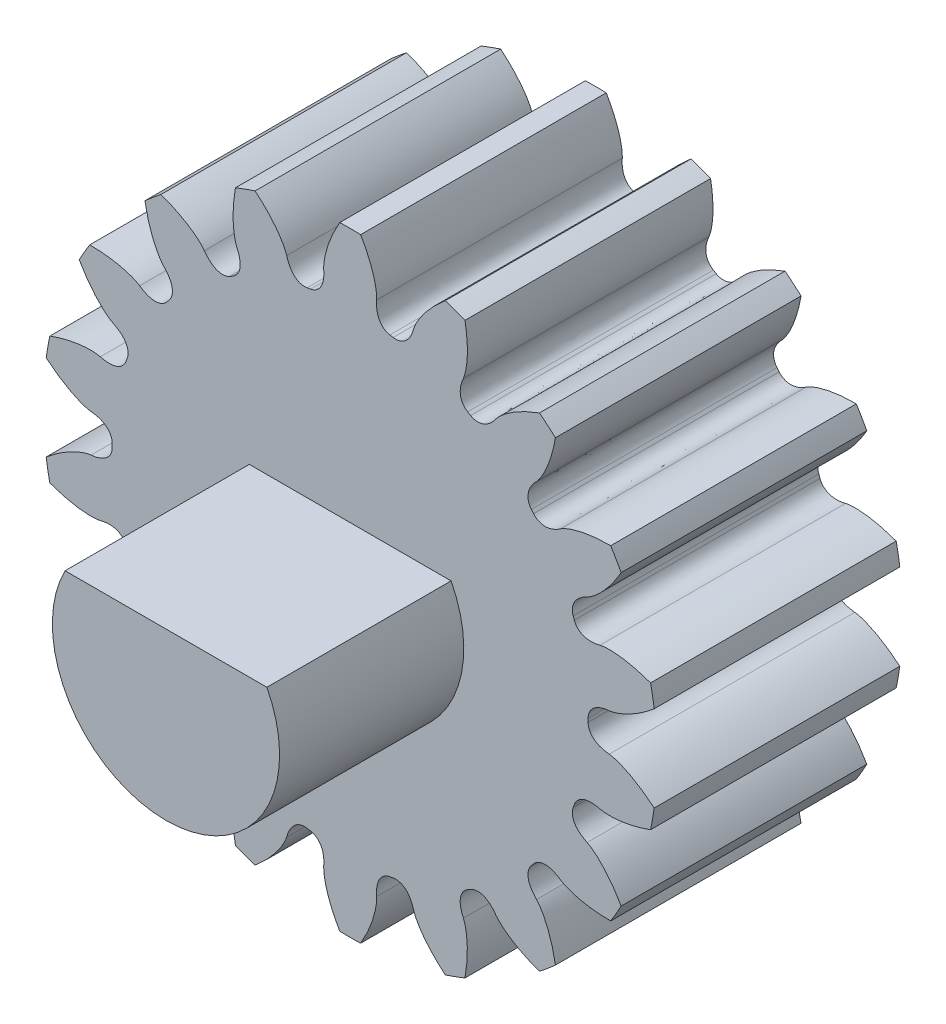
SolidWorks part; units mm, degrees
ref_plane "Спереди" through (0, 0, 0) normal (0, 0, 1) x (1, 0, 0)
ref_plane "Сверху" through (0, 0, 0) normal (0, 1, 0) x (1, 0, 0)
ref_plane "Справа" through (0, 0, 0) normal (1, 0, 0) x (0, 0, -1)
sketch "Sketch1" plane through (0, 0, 0) normal (0, 0, 1) x (1, 0, 0)
  circle A0 centre (0, 0) radius 5.5
extrude "Extrude1" add sketch "Sketch1" along normal blind 4
sketch "Sketch2" plane through (0, 0, 4) normal (0, 0, 1) x (1, 0, 0)
  line L0 (1.6432, 0.85) -> (-1.6432, 0.85)
  line L1 (1.7321, 1) -> (-1.7321, 1)
  arc A0 (-1.7321, 1) -> (1.7321, 1) centre (0, 0) ccw
  arc A1 (-1.6432, 0.85) -> (1.6432, 0.85) centre (0, 0) ccw
  dimension "D1" = 0.15
extrude "Extrude2" add sketch "Sketch2" along normal blind 3 contours L0 A1 region at (0, -0.3518, 4)
sketch "Sketch3" plane through (0, 0, 0) normal (0, 0, -1) x (-1, 0, 0)
  line L0 (1.1832, 1.15) -> (-1.1832, 1.15)
  line L1 (1.118, 1) -> (-1.118, 1)
  arc A0 (-1.118, 1) -> (1.118, 1) centre (0, 0) ccw
  arc A1 (-1.1832, 1.15) -> (1.1832, 1.15) centre (0, 0) ccw
  dimension "D1" = 0.15
extrude "Extrude3" cut sketch "Sketch3" against normal blind 3.5 contours L1 A0 | A0 L1 | L0 A1 A0 L1 region at (0, -1.6067, 0) region at (0, -0.148, 0)
sketch "Sketch4" plane through (0, 0, 0) normal (0, 0, 1) x (1, 0, 0)
  line L0 (0, 0) -> (0, 6.5) construction
  line L1 (0, 0) -> (0, -6.5) construction
  line L2 (0, 0) -> (-6.5, 0) construction
  line L3 (0, 0) -> (6.5, 0) construction
  arc A28 (-0.6456, 3.8208) -> (-0.7002, 3.8112) centre (0, 0) ccw
  arc A30 (-1.549, 4.754) -> (-1.8692, 4.6375) centre (0, 0) ccw
  arc A31 (-1.9135, 3.3696) -> (-1.9614, 3.3419) centre (0, 0) ccw
  arc A32 (-3.0816, 3.9375) -> (-3.3426, 3.7185) centre (0, 0) ccw
  arc A33 (-2.9505, 2.512) -> (-2.9862, 2.4695) centre (0, 0) ccw
  arc A34 (-4.2424, 2.6461) -> (-4.4128, 2.351) centre (0, 0) ccw
  arc A35 (-3.6317, 1.3513) -> (-3.6507, 1.2993) centre (0, 0) ccw
  arc A36 (-4.8916, 1.0355) -> (-4.9508, 0.6999) centre (0, 0) ccw
  arc A37 (-3.8749, 0.0277) -> (-3.8749, -0.0277) centre (0, 0) ccw
  arc A38 (-4.9508, -0.6999) -> (-4.8916, -1.0355) centre (0, 0) ccw
  arc A39 (-3.6507, -1.2993) -> (-3.6317, -1.3513) centre (0, 0) ccw
  arc A40 (-4.4128, -2.351) -> (-4.2424, -2.6461) centre (0, 0) ccw
  arc A41 (-2.9862, -2.4695) -> (-2.9505, -2.512) centre (0, 0) ccw
  arc A42 (-3.3426, -3.7185) -> (-3.0816, -3.9375) centre (0, 0) ccw
  arc A43 (-1.9614, -3.3419) -> (-1.9135, -3.3696) centre (0, 0) ccw
  arc A44 (-1.8692, -4.6375) -> (-1.549, -4.754) centre (0, 0) ccw
  arc A45 (-0.7002, -3.8112) -> (-0.6456, -3.8208) centre (0, 0) ccw
  arc A46 (-0.1704, -4.9971) -> (0.1704, -4.9971) centre (0, 0) ccw
  arc A47 (0.6456, -3.8208) -> (0.7002, -3.8112) centre (0, 0) ccw
  arc A48 (1.549, -4.754) -> (1.8692, -4.6375) centre (0, 0) ccw
  arc A49 (1.9135, -3.3696) -> (1.9614, -3.3419) centre (0, 0) ccw
  arc A50 (3.0816, -3.9375) -> (3.3426, -3.7185) centre (0, 0) ccw
  arc A51 (2.9505, -2.512) -> (2.9862, -2.4695) centre (0, 0) ccw
  arc A52 (4.2424, -2.6461) -> (4.4128, -2.351) centre (0, 0) ccw
  arc A53 (3.6317, -1.3513) -> (3.6507, -1.2993) centre (0, 0) ccw
  arc A54 (4.8916, -1.0355) -> (4.9508, -0.6999) centre (0, 0) ccw
  arc A55 (3.8749, -0.0277) -> (3.8749, 0.0277) centre (0, 0) ccw
  arc A56 (4.9508, 0.6999) -> (4.8916, 1.0355) centre (0, 0) ccw
  arc A57 (3.6507, 1.2993) -> (3.6317, 1.3513) centre (0, 0) ccw
  arc A58 (4.4128, 2.351) -> (4.2424, 2.6461) centre (0, 0) ccw
  arc A59 (2.9862, 2.4695) -> (2.9505, 2.512) centre (0, 0) ccw
  arc A60 (3.3426, 3.7185) -> (3.0816, 3.9375) centre (0, 0) ccw
  arc A61 (1.9614, 3.3419) -> (1.9135, 3.3696) centre (0, 0) ccw
  arc A62 (1.8692, 4.6375) -> (1.549, 4.754) centre (0, 0) ccw
  arc A63 (0.7002, 3.8112) -> (0.6456, 3.8208) centre (0, 0) ccw
  circle A64 centre (0, 0) radius 4.5 construction
  arc A65 (0.1704, 4.9971) -> (-0.1704, 4.9971) centre (0, 0) ccw
  circle A66 centre (0, 0) radius 6.3388
  spline S0 degree 3 poles (0.4314, 4.2073) (0.4264, 4.1628) (0.4271, 4.1189) (0.4335, 4.0758) (0.4372, 4.0511) (0.4421, 4.026) (0.4501, 4.0023) (0.4558, 3.9851) (0.4628, 3.968) (0.4713, 3.952) (0.4783, 3.9388) (0.4864, 3.9259) (0.4954, 3.914) (0.5034, 3.9034) (0.5123, 3.8933) (0.5218, 3.8841) (0.5307, 3.8755) (0.5403, 3.8675) (0.5504, 3.8604) (0.56, 3.8536) (0.5702, 3.8474) (0.5807, 3.8421) (0.5909, 3.837) (0.6017, 3.8326) (0.6125, 3.829) (0.6233, 3.8255) (0.6343, 3.8228) (0.6456, 3.8208) knots 0 0 0 0 1 1 1 2 2 2 3 3 3 4 4 4 5 5 5 6 6 6 7 7 7 8 8 8 9 9 9 9
  spline S1 degree 3 poles (-0.4314, 4.2073) (-0.4264, 4.1628) (-0.4271, 4.1189) (-0.4335, 4.0758) (-0.4372, 4.0511) (-0.4421, 4.026) (-0.4501, 4.0023) (-0.4558, 3.9851) (-0.4628, 3.968) (-0.4713, 3.952) (-0.4783, 3.9388) (-0.4864, 3.9259) (-0.4954, 3.914) (-0.5034, 3.9034) (-0.5123, 3.8933) (-0.5218, 3.8841) (-0.5307, 3.8755) (-0.5403, 3.8675) (-0.5504, 3.8604) (-0.56, 3.8536) (-0.5702, 3.8474) (-0.5807, 3.8421) (-0.5909, 3.837) (-0.6017, 3.8326) (-0.6125, 3.829) (-0.6233, 3.8255) (-0.6343, 3.8228) (-0.6456, 3.8208) knots 0 0 0 0 1 1 1 2 2 2 3 3 3 4 4 4 5 5 5 6 6 6 7 7 7 8 8 8 9 9 9 9
  spline S2 degree 3 poles (0.4314, 4.2073) (0.432, 4.2362) (0.431, 4.265) (0.4284, 4.2936) (0.4258, 4.3229) (0.4209, 4.352) (0.4156, 4.3809) (0.4101, 4.4104) (0.4034, 4.4397) (0.3959, 4.4687) (0.3884, 4.4983) (0.3797, 4.5277) (0.3705, 4.5568) (0.361, 4.5865) (0.3507, 4.6159) (0.3398, 4.6451) (0.3287, 4.6748) (0.3167, 4.7042) (0.3042, 4.7333) (0.2915, 4.763) (0.278, 4.7924) (0.264, 4.8215) (0.2497, 4.8511) (0.2348, 4.8805) (0.2193, 4.9095) (0.2036, 4.939) (0.1873, 4.9682) (0.1704, 4.9971) knots 0 0 0 0 1 1 1 2 2 2 3 3 3 4 4 4 5 5 5 6 6 6 7 7 7 8 8 8 9 9 9 9
  spline S3 degree 3 poles (-0.4314, 4.2073) (-0.432, 4.2362) (-0.431, 4.265) (-0.4284, 4.2936) (-0.4258, 4.3229) (-0.4209, 4.352) (-0.4156, 4.3809) (-0.4101, 4.4104) (-0.4034, 4.4397) (-0.3959, 4.4687) (-0.3884, 4.4983) (-0.3797, 4.5277) (-0.3705, 4.5568) (-0.361, 4.5865) (-0.3507, 4.6159) (-0.3398, 4.6451) (-0.3287, 4.6748) (-0.3167, 4.7042) (-0.3042, 4.7333) (-0.2915, 4.763) (-0.278, 4.7924) (-0.264, 4.8215) (-0.2497, 4.8511) (-0.2348, 4.8805) (-0.2193, 4.9095) (-0.2036, 4.939) (-0.1873, 4.9682) (-0.1704, 4.9971) knots 0 0 0 0 1 1 1 2 2 2 3 3 3 4 4 4 5 5 5 6 6 6 7 7 7 8 8 8 9 9 9 9
  spline S4 degree 3 poles (-1.0336, 4.1011) (-1.0231, 4.0576) (-1.0074, 4.0166) (-0.9866, 3.9783) (-0.9747, 3.9563) (-0.9616, 3.9344) (-0.9459, 3.9148) (-0.9346, 3.9007) (-0.9223, 3.887) (-0.9088, 3.8748) (-0.8977, 3.8649) (-0.8857, 3.8555) (-0.8732, 3.8474) (-0.862, 3.8402) (-0.8502, 3.8337) (-0.8381, 3.8283) (-0.8268, 3.8233) (-0.8151, 3.819) (-0.8032, 3.8158) (-0.7918, 3.8127) (-0.7801, 3.8104) (-0.7684, 3.809) (-0.757, 3.8077) (-0.7454, 3.8072) (-0.734, 3.8076) (-0.7227, 3.808) (-0.7114, 3.8092) (-0.7002, 3.8112) knots 0 0 0 0 1 1 1 2 2 2 3 3 3 4 4 4 5 5 5 6 6 6 7 7 7 8 8 8 9 9 9 9
  spline S5 degree 3 poles (-1.8443, 3.806) (-1.8244, 3.7659) (-1.8101, 3.7245) (-1.8014, 3.6817) (-1.7963, 3.6572) (-1.7924, 3.632) (-1.7918, 3.607) (-1.7913, 3.5888) (-1.792, 3.5704) (-1.7945, 3.5525) (-1.7966, 3.5377) (-1.7998, 3.5228) (-1.8042, 3.5085) (-1.8081, 3.4958) (-1.813, 3.4833) (-1.8188, 3.4714) (-1.8242, 3.4603) (-1.8305, 3.4495) (-1.8375, 3.4393) (-1.8442, 3.4297) (-1.8517, 3.4204) (-1.8598, 3.4118) (-1.8676, 3.4035) (-1.8762, 3.3956) (-1.8852, 3.3886) (-1.8941, 3.3816) (-1.9035, 3.3753) (-1.9135, 3.3696) knots 0 0 0 0 1 1 1 2 2 2 3 3 3 4 4 4 5 5 5 6 6 6 7 7 7 8 8 8 9 9 9 9
  spline S6 degree 3 poles (-1.0336, 4.1011) (-1.043, 4.1285) (-1.0537, 4.1552) (-1.066, 4.1812) (-1.0784, 4.2078) (-1.093, 4.2335) (-1.1079, 4.2588) (-1.123, 4.2847) (-1.1394, 4.3099) (-1.1563, 4.3346) (-1.1736, 4.3599) (-1.1917, 4.3845) (-1.2104, 4.4087) (-1.2294, 4.4334) (-1.2492, 4.4575) (-1.2694, 4.4811) (-1.29, 4.5052) (-1.3113, 4.5288) (-1.333, 4.5519) (-1.3551, 4.5755) (-1.3779, 4.5985) (-1.401, 4.621) (-1.4245, 4.644) (-1.4486, 4.6664) (-1.473, 4.6884) (-1.4979, 4.7108) (-1.5232, 4.7326) (-1.549, 4.754) knots 0 0 0 0 1 1 1 2 2 2 3 3 3 4 4 4 5 5 5 6 6 6 7 7 7 8 8 8 9 9 9 9
  spline S7 degree 3 poles (-1.8443, 3.806) (-1.8548, 3.833) (-1.8637, 3.8604) (-1.8711, 3.8882) (-1.8786, 3.9166) (-1.884, 3.9456) (-1.8889, 3.9746) (-1.8938, 4.0041) (-1.8975, 4.034) (-1.9004, 4.0638) (-1.9034, 4.0942) (-1.9054, 4.1248) (-1.9067, 4.1553) (-1.9079, 4.1864) (-1.9083, 4.2176) (-1.908, 4.2487) (-1.9077, 4.2804) (-1.9065, 4.3122) (-1.9048, 4.3438) (-1.903, 4.3761) (-1.9004, 4.4083) (-1.8971, 4.4404) (-1.8939, 4.4732) (-1.8899, 4.5058) (-1.8853, 4.5384) (-1.8806, 4.5715) (-1.8752, 4.6045) (-1.8692, 4.6375) knots 0 0 0 0 1 1 1 2 2 2 3 3 3 4 4 4 5 5 5 6 6 6 7 7 7 8 8 8 9 9 9 9
  spline S8 degree 3 poles (-2.3739, 3.5002) (-2.3491, 3.463) (-2.3204, 3.4298) (-2.2878, 3.4009) (-2.2691, 3.3843) (-2.2492, 3.3682) (-2.2278, 3.3552) (-2.2124, 3.3458) (-2.1961, 3.3371) (-2.1792, 3.3303) (-2.1654, 3.3248) (-2.151, 3.32) (-2.1364, 3.3167) (-2.1234, 3.3138) (-2.1101, 3.3117) (-2.0969, 3.3108) (-2.0846, 3.3099) (-2.0721, 3.31) (-2.0598, 3.311) (-2.0481, 3.312) (-2.0363, 3.3138) (-2.0248, 3.3165) (-2.0137, 3.3191) (-2.0026, 3.3226) (-1.992, 3.3269) (-1.9815, 3.3311) (-1.9713, 3.3361) (-1.9614, 3.3419) knots 0 0 0 0 1 1 1 2 2 2 3 3 3 4 4 4 5 5 5 6 6 6 7 7 7 8 8 8 9 9 9 9
  spline S9 degree 3 poles (-3.0348, 2.9457) (-3.0024, 2.9148) (-2.9748, 2.8807) (-2.952, 2.8436) (-2.9389, 2.8223) (-2.9265, 2.7999) (-2.9174, 2.7766) (-2.9108, 2.7597) (-2.9051, 2.7422) (-2.9013, 2.7245) (-2.8982, 2.7098) (-2.8961, 2.6948) (-2.8954, 2.6799) (-2.8947, 2.6666) (-2.895, 2.6531) (-2.8964, 2.6399) (-2.8977, 2.6277) (-2.8999, 2.6154) (-2.903, 2.6035) (-2.906, 2.5921) (-2.9098, 2.5808) (-2.9145, 2.57) (-2.919, 2.5595) (-2.9244, 2.5492) (-2.9305, 2.5394) (-2.9364, 2.5298) (-2.9431, 2.5207) (-2.9505, 2.512) knots 0 0 0 0 1 1 1 2 2 2 3 3 3 4 4 4 5 5 5 6 6 6 7 7 7 8 8 8 9 9 9 9
  spline S10 degree 3 poles (-2.3739, 3.5002) (-2.3921, 3.5228) (-2.4113, 3.5442) (-2.4317, 3.5645) (-2.4525, 3.5852) (-2.475, 3.6044) (-2.4977, 3.6231) (-2.5208, 3.6422) (-2.5448, 3.6603) (-2.5691, 3.6777) (-2.594, 3.6955) (-2.6195, 3.7125) (-2.6453, 3.7289) (-2.6716, 3.7455) (-2.6984, 3.7614) (-2.7255, 3.7767) (-2.7531, 3.7923) (-2.7812, 3.8072) (-2.8095, 3.8215) (-2.8383, 3.836) (-2.8675, 3.8499) (-2.897, 3.8632) (-2.9269, 3.8767) (-2.9572, 3.8896) (-2.9877, 3.9019) (-3.0187, 3.9144) (-3.05, 3.9263) (-3.0816, 3.9375) knots 0 0 0 0 1 1 1 2 2 2 3 3 3 4 4 4 5 5 5 6 6 6 7 7 7 8 8 8 9 9 9 9
  spline S11 degree 3 poles (-3.0348, 2.9457) (-3.0539, 2.9675) (-3.0716, 2.9902) (-3.0881, 3.0137) (-3.1049, 3.0378) (-3.1199, 3.0633) (-3.1343, 3.0889) (-3.1491, 3.1149) (-3.1627, 3.1417) (-3.1757, 3.1687) (-3.189, 3.1963) (-3.2012, 3.2243) (-3.2129, 3.2526) (-3.2247, 3.2814) (-3.2357, 3.3106) (-3.2461, 3.3399) (-3.2566, 3.3698) (-3.2664, 3.4) (-3.2756, 3.4304) (-3.2849, 3.4613) (-3.2935, 3.4925) (-3.3015, 3.5238) (-3.3096, 3.5557) (-3.317, 3.5877) (-3.3238, 3.6199) (-3.3307, 3.6526) (-3.337, 3.6855) (-3.3426, 3.7185) knots 0 0 0 0 1 1 1 2 2 2 3 3 3 4 4 4 5 5 5 6 6 6 7 7 7 8 8 8 9 9 9 9
  spline S12 degree 3 poles (-3.4279, 2.4772) (-3.3919, 2.4507) (-3.3535, 2.4294) (-3.313, 2.4133) (-3.2897, 2.4041) (-3.2656, 2.3958) (-3.241, 2.3909) (-3.2233, 2.3873) (-3.205, 2.3848) (-3.1869, 2.3842) (-3.1719, 2.3837) (-3.1568, 2.3841) (-3.1419, 2.386) (-3.1288, 2.3877) (-3.1155, 2.3903) (-3.1028, 2.3939) (-3.0909, 2.3974) (-3.0792, 2.4017) (-3.068, 2.4068) (-3.0573, 2.4117) (-3.0469, 2.4175) (-3.037, 2.424) (-3.0275, 2.4303) (-3.0183, 2.4373) (-3.0097, 2.445) (-3.0013, 2.4525) (-2.9935, 2.4607) (-2.9862, 2.4695) knots 0 0 0 0 1 1 1 2 2 2 3 3 3 4 4 4 5 5 5 6 6 6 7 7 7 8 8 8 9 9 9 9
  spline S13 degree 3 poles (-3.8593, 1.7301) (-3.8183, 1.7121) (-3.7807, 1.6896) (-3.7465, 1.6625) (-3.7269, 1.6469) (-3.7076, 1.6301) (-3.6911, 1.6114) (-3.6791, 1.5978) (-3.6678, 1.5832) (-3.6582, 1.5678) (-3.6503, 1.5551) (-3.6431, 1.5418) (-3.6373, 1.528) (-3.6322, 1.5157) (-3.6278, 1.503) (-3.6246, 1.4901) (-3.6216, 1.4782) (-3.6195, 1.4658) (-3.6184, 1.4536) (-3.6173, 1.4419) (-3.617, 1.4299) (-3.6177, 1.4182) (-3.6184, 1.4067) (-3.6199, 1.3952) (-3.6223, 1.384) (-3.6246, 1.373) (-3.6278, 1.3621) (-3.6317, 1.3513) knots 0 0 0 0 1 1 1 2 2 2 3 3 3 4 4 4 5 5 5 6 6 6 7 7 7 8 8 8 9 9 9 9
  spline S14 degree 3 poles (-3.4279, 2.4772) (-3.4527, 2.4922) (-3.4781, 2.5057) (-3.5042, 2.5178) (-3.5308, 2.5302) (-3.5585, 2.5405) (-3.5862, 2.5504) (-3.6144, 2.5604) (-3.6432, 2.5691) (-3.6721, 2.5772) (-3.7015, 2.5855) (-3.7312, 2.5927) (-3.7611, 2.5992) (-3.7915, 2.6059) (-3.8221, 2.6117) (-3.8529, 2.6168) (-3.8841, 2.622) (-3.9156, 2.6264) (-3.9471, 2.6301) (-3.9792, 2.6339) (-4.0113, 2.637) (-4.0436, 2.6394) (-4.0763, 2.6419) (-4.1092, 2.6436) (-4.1421, 2.6447) (-4.1755, 2.6458) (-4.2089, 2.6463) (-4.2424, 2.6461) knots 0 0 0 0 1 1 1 2 2 2 3 3 3 4 4 4 5 5 5 6 6 6 7 7 7 8 8 8 9 9 9 9
  spline S15 degree 3 poles (-3.8593, 1.7301) (-3.8846, 1.744) (-3.9091, 1.7593) (-3.9326, 1.7758) (-3.9566, 1.7927) (-3.9794, 1.8115) (-4.0018, 1.8306) (-4.0246, 1.85) (-4.0465, 1.8705) (-4.068, 1.8915) (-4.0898, 1.9128) (-4.111, 1.935) (-4.1316, 1.9576) (-4.1525, 1.9806) (-4.1729, 2.0042) (-4.1926, 2.0283) (-4.2128, 2.0528) (-4.2323, 2.0778) (-4.2513, 2.1032) (-4.2706, 2.1291) (-4.2894, 2.1554) (-4.3076, 2.1821) (-4.3261, 2.2093) (-4.344, 2.2369) (-4.3614, 2.2648) (-4.3791, 2.2932) (-4.3962, 2.3219) (-4.4128, 2.351) knots 0 0 0 0 1 1 1 2 2 2 3 3 3 4 4 4 5 5 5 6 6 6 7 7 7 8 8 8 9 9 9 9
  spline S16 degree 3 poles (-4.0684, 1.1554) (-4.0255, 1.1428) (-3.9822, 1.1359) (-3.9386, 1.1347) (-3.9136, 1.134) (-3.888, 1.1345) (-3.8633, 1.1382) (-3.8454, 1.1409) (-3.8273, 1.1448) (-3.8101, 1.1504) (-3.7959, 1.155) (-3.7818, 1.1607) (-3.7685, 1.1675) (-3.7567, 1.1736) (-3.7452, 1.1806) (-3.7344, 1.1884) (-3.7245, 1.1956) (-3.7149, 1.2037) (-3.7062, 1.2123) (-3.6978, 1.2206) (-3.69, 1.2296) (-3.6829, 1.239) (-3.6761, 1.2482) (-3.6699, 1.258) (-3.6645, 1.2681) (-3.6591, 1.2781) (-3.6545, 1.2885) (-3.6507, 1.2993) knots 0 0 0 0 1 1 1 2 2 2 3 3 3 4 4 4 5 5 5 6 6 6 7 7 7 8 8 8 9 9 9 9
  spline S17 degree 3 poles (-4.2183, 0.3058) (-4.1736, 0.3029) (-4.1305, 0.2946) (-4.0892, 0.2808) (-4.0654, 0.2729) (-4.0416, 0.2637) (-4.0196, 0.2518) (-4.0037, 0.2431) (-3.9881, 0.2333) (-3.9738, 0.2221) (-3.962, 0.2129) (-3.9507, 0.2028) (-3.9406, 0.1918) (-3.9315, 0.1821) (-3.9231, 0.1716) (-3.9157, 0.1606) (-3.9088, 0.1503) (-3.9026, 0.1395) (-3.8973, 0.1284) (-3.8923, 0.1177) (-3.888, 0.1066) (-3.8846, 0.0953) (-3.8813, 0.0843) (-3.8788, 0.073) (-3.8772, 0.0617) (-3.8756, 0.0505) (-3.8748, 0.0391) (-3.8749, 0.0277) knots 0 0 0 0 1 1 1 2 2 2 3 3 3 4 4 4 5 5 5 6 6 6 7 7 7 8 8 8 9 9 9 9
  spline S18 degree 3 poles (-4.0684, 1.1554) (-4.0968, 1.161) (-4.1254, 1.165) (-4.154, 1.1675) (-4.1833, 1.17) (-4.2128, 1.1702) (-4.2422, 1.17) (-4.2722, 1.1698) (-4.3022, 1.1682) (-4.3321, 1.1659) (-4.3625, 1.1636) (-4.393, 1.1602) (-4.4232, 1.1561) (-4.4541, 1.152) (-4.4849, 1.1469) (-4.5155, 1.1412) (-4.5467, 1.1354) (-4.5777, 1.1288) (-4.6086, 1.1215) (-4.64, 1.1141) (-4.6713, 1.106) (-4.7024, 1.0972) (-4.7341, 1.0883) (-4.7655, 1.0787) (-4.7968, 1.0685) (-4.8286, 1.0582) (-4.8602, 1.0472) (-4.8916, 1.0355) knots 0 0 0 0 1 1 1 2 2 2 3 3 3 4 4 4 5 5 5 6 6 6 7 7 7 8 8 8 9 9 9 9
  spline S19 degree 3 poles (-4.2183, 0.3058) (-4.2468, 0.3102) (-4.275, 0.3162) (-4.3028, 0.3237) (-4.3311, 0.3314) (-4.359, 0.3412) (-4.3865, 0.3515) (-4.4146, 0.362) (-4.4423, 0.3737) (-4.4696, 0.3861) (-4.4974, 0.3987) (-4.5248, 0.4123) (-4.5519, 0.4264) (-4.5795, 0.4409) (-4.6067, 0.4562) (-4.6335, 0.472) (-4.6608, 0.4881) (-4.6877, 0.505) (-4.7143, 0.5223) (-4.7413, 0.54) (-4.7679, 0.5584) (-4.7941, 0.5773) (-4.8208, 0.5964) (-4.8471, 0.6162) (-4.873, 0.6365) (-4.8993, 0.6571) (-4.9252, 0.6783) (-4.9508, 0.6999) knots 0 0 0 0 1 1 1 2 2 2 3 3 3 4 4 4 5 5 5 6 6 6 7 7 7 8 8 8 9 9 9 9
  spline S20 degree 3 poles (-4.2183, -0.3058) (-4.1736, -0.3029) (-4.1305, -0.2946) (-4.0892, -0.2808) (-4.0654, -0.2729) (-4.0416, -0.2637) (-4.0196, -0.2518) (-4.0037, -0.2431) (-3.9881, -0.2333) (-3.9738, -0.2221) (-3.962, -0.2129) (-3.9507, -0.2028) (-3.9406, -0.1918) (-3.9315, -0.1821) (-3.9231, -0.1716) (-3.9157, -0.1606) (-3.9088, -0.1503) (-3.9026, -0.1395) (-3.8973, -0.1284) (-3.8923, -0.1177) (-3.888, -0.1066) (-3.8846, -0.0953) (-3.8813, -0.0843) (-3.8788, -0.073) (-3.8772, -0.0617) (-3.8756, -0.0505) (-3.8748, -0.0391) (-3.8749, -0.0277) knots 0 0 0 0 1 1 1 2 2 2 3 3 3 4 4 4 5 5 5 6 6 6 7 7 7 8 8 8 9 9 9 9
  spline S21 degree 3 poles (-4.0684, -1.1554) (-4.0255, -1.1428) (-3.9822, -1.1359) (-3.9386, -1.1347) (-3.9136, -1.134) (-3.888, -1.1345) (-3.8633, -1.1382) (-3.8454, -1.1409) (-3.8273, -1.1448) (-3.8101, -1.1504) (-3.7959, -1.155) (-3.7818, -1.1607) (-3.7685, -1.1675) (-3.7567, -1.1736) (-3.7452, -1.1806) (-3.7344, -1.1884) (-3.7245, -1.1956) (-3.7149, -1.2037) (-3.7062, -1.2123) (-3.6978, -1.2206) (-3.69, -1.2296) (-3.6829, -1.239) (-3.6761, -1.2482) (-3.6699, -1.258) (-3.6645, -1.2681) (-3.6591, -1.2781) (-3.6545, -1.2885) (-3.6507, -1.2993) knots 0 0 0 0 1 1 1 2 2 2 3 3 3 4 4 4 5 5 5 6 6 6 7 7 7 8 8 8 9 9 9 9
  spline S22 degree 3 poles (-4.2183, -0.3058) (-4.2468, -0.3102) (-4.275, -0.3162) (-4.3028, -0.3237) (-4.3311, -0.3314) (-4.359, -0.3412) (-4.3865, -0.3515) (-4.4146, -0.362) (-4.4423, -0.3737) (-4.4696, -0.3861) (-4.4974, -0.3987) (-4.5248, -0.4123) (-4.5519, -0.4264) (-4.5795, -0.4409) (-4.6067, -0.4562) (-4.6335, -0.472) (-4.6608, -0.4881) (-4.6877, -0.505) (-4.7143, -0.5223) (-4.7413, -0.54) (-4.7679, -0.5584) (-4.7941, -0.5773) (-4.8208, -0.5964) (-4.8471, -0.6162) (-4.873, -0.6365) (-4.8993, -0.6571) (-4.9252, -0.6783) (-4.9508, -0.6999) knots 0 0 0 0 1 1 1 2 2 2 3 3 3 4 4 4 5 5 5 6 6 6 7 7 7 8 8 8 9 9 9 9
  spline S23 degree 3 poles (-4.0684, -1.1554) (-4.0968, -1.161) (-4.1254, -1.165) (-4.154, -1.1675) (-4.1833, -1.17) (-4.2128, -1.1702) (-4.2422, -1.17) (-4.2722, -1.1698) (-4.3022, -1.1682) (-4.3321, -1.1659) (-4.3625, -1.1636) (-4.393, -1.1602) (-4.4232, -1.1561) (-4.4541, -1.152) (-4.4849, -1.1469) (-4.5155, -1.1412) (-4.5467, -1.1354) (-4.5777, -1.1288) (-4.6086, -1.1215) (-4.64, -1.1141) (-4.6713, -1.106) (-4.7024, -1.0972) (-4.7341, -1.0883) (-4.7655, -1.0787) (-4.7968, -1.0685) (-4.8286, -1.0582) (-4.8602, -1.0472) (-4.8916, -1.0355) knots 0 0 0 0 1 1 1 2 2 2 3 3 3 4 4 4 5 5 5 6 6 6 7 7 7 8 8 8 9 9 9 9
  spline S24 degree 3 poles (-3.8593, -1.7301) (-3.8183, -1.7121) (-3.7807, -1.6896) (-3.7465, -1.6625) (-3.7269, -1.6469) (-3.7076, -1.6301) (-3.6911, -1.6114) (-3.6791, -1.5978) (-3.6678, -1.5832) (-3.6582, -1.5678) (-3.6503, -1.5551) (-3.6431, -1.5418) (-3.6373, -1.528) (-3.6322, -1.5157) (-3.6278, -1.503) (-3.6246, -1.4901) (-3.6216, -1.4782) (-3.6195, -1.4658) (-3.6184, -1.4536) (-3.6173, -1.4419) (-3.617, -1.4299) (-3.6177, -1.4182) (-3.6184, -1.4067) (-3.6199, -1.3952) (-3.6223, -1.384) (-3.6246, -1.373) (-3.6278, -1.3621) (-3.6317, -1.3513) knots 0 0 0 0 1 1 1 2 2 2 3 3 3 4 4 4 5 5 5 6 6 6 7 7 7 8 8 8 9 9 9 9
  spline S25 degree 3 poles (-3.4279, -2.4772) (-3.3919, -2.4507) (-3.3535, -2.4294) (-3.313, -2.4133) (-3.2897, -2.4041) (-3.2656, -2.3958) (-3.241, -2.3909) (-3.2233, -2.3873) (-3.205, -2.3848) (-3.1869, -2.3842) (-3.1719, -2.3837) (-3.1568, -2.3841) (-3.1419, -2.386) (-3.1288, -2.3877) (-3.1155, -2.3903) (-3.1028, -2.3939) (-3.0909, -2.3974) (-3.0792, -2.4017) (-3.068, -2.4068) (-3.0573, -2.4117) (-3.0469, -2.4175) (-3.037, -2.424) (-3.0275, -2.4303) (-3.0183, -2.4373) (-3.0097, -2.445) (-3.0013, -2.4525) (-2.9935, -2.4607) (-2.9862, -2.4695) knots 0 0 0 0 1 1 1 2 2 2 3 3 3 4 4 4 5 5 5 6 6 6 7 7 7 8 8 8 9 9 9 9
  spline S26 degree 3 poles (-3.8593, -1.7301) (-3.8846, -1.744) (-3.9091, -1.7593) (-3.9326, -1.7758) (-3.9566, -1.7927) (-3.9794, -1.8115) (-4.0018, -1.8306) (-4.0246, -1.85) (-4.0465, -1.8705) (-4.068, -1.8915) (-4.0898, -1.9128) (-4.111, -1.935) (-4.1316, -1.9576) (-4.1525, -1.9806) (-4.1729, -2.0042) (-4.1926, -2.0283) (-4.2128, -2.0528) (-4.2323, -2.0778) (-4.2513, -2.1032) (-4.2706, -2.1291) (-4.2894, -2.1554) (-4.3076, -2.1821) (-4.3261, -2.2093) (-4.344, -2.2369) (-4.3614, -2.2648) (-4.3791, -2.2932) (-4.3962, -2.3219) (-4.4128, -2.351) knots 0 0 0 0 1 1 1 2 2 2 3 3 3 4 4 4 5 5 5 6 6 6 7 7 7 8 8 8 9 9 9 9
  spline S27 degree 3 poles (-3.4279, -2.4772) (-3.4527, -2.4922) (-3.4781, -2.5057) (-3.5042, -2.5178) (-3.5308, -2.5302) (-3.5585, -2.5405) (-3.5862, -2.5504) (-3.6144, -2.5604) (-3.6432, -2.5691) (-3.6721, -2.5772) (-3.7015, -2.5855) (-3.7312, -2.5927) (-3.7611, -2.5992) (-3.7915, -2.6059) (-3.8221, -2.6117) (-3.8529, -2.6168) (-3.8841, -2.622) (-3.9156, -2.6264) (-3.9471, -2.6301) (-3.9792, -2.6339) (-4.0113, -2.637) (-4.0436, -2.6394) (-4.0763, -2.6419) (-4.1092, -2.6436) (-4.1421, -2.6447) (-4.1755, -2.6458) (-4.2089, -2.6463) (-4.2424, -2.6461) knots 0 0 0 0 1 1 1 2 2 2 3 3 3 4 4 4 5 5 5 6 6 6 7 7 7 8 8 8 9 9 9 9
  spline S28 degree 3 poles (-3.0348, -2.9457) (-3.0024, -2.9148) (-2.9748, -2.8807) (-2.952, -2.8436) (-2.9389, -2.8223) (-2.9265, -2.7999) (-2.9174, -2.7766) (-2.9108, -2.7597) (-2.9051, -2.7422) (-2.9013, -2.7245) (-2.8982, -2.7098) (-2.8961, -2.6948) (-2.8954, -2.6799) (-2.8947, -2.6666) (-2.895, -2.6531) (-2.8964, -2.6399) (-2.8977, -2.6277) (-2.8999, -2.6154) (-2.903, -2.6035) (-2.906, -2.5921) (-2.9098, -2.5808) (-2.9145, -2.57) (-2.919, -2.5595) (-2.9244, -2.5492) (-2.9305, -2.5394) (-2.9364, -2.5298) (-2.9431, -2.5207) (-2.9505, -2.512) knots 0 0 0 0 1 1 1 2 2 2 3 3 3 4 4 4 5 5 5 6 6 6 7 7 7 8 8 8 9 9 9 9
  spline S29 degree 3 poles (-2.3739, -3.5002) (-2.3491, -3.463) (-2.3204, -3.4298) (-2.2878, -3.4009) (-2.2691, -3.3843) (-2.2492, -3.3682) (-2.2278, -3.3552) (-2.2124, -3.3458) (-2.1961, -3.3371) (-2.1792, -3.3303) (-2.1654, -3.3248) (-2.151, -3.32) (-2.1364, -3.3167) (-2.1234, -3.3138) (-2.1101, -3.3117) (-2.0969, -3.3108) (-2.0846, -3.3099) (-2.0721, -3.31) (-2.0598, -3.311) (-2.0481, -3.312) (-2.0363, -3.3138) (-2.0248, -3.3165) (-2.0137, -3.3191) (-2.0026, -3.3226) (-1.992, -3.3269) (-1.9815, -3.3311) (-1.9713, -3.3361) (-1.9614, -3.3419) knots 0 0 0 0 1 1 1 2 2 2 3 3 3 4 4 4 5 5 5 6 6 6 7 7 7 8 8 8 9 9 9 9
  spline S30 degree 3 poles (-3.0348, -2.9457) (-3.0539, -2.9675) (-3.0716, -2.9902) (-3.0881, -3.0137) (-3.1049, -3.0378) (-3.1199, -3.0633) (-3.1343, -3.0889) (-3.1491, -3.1149) (-3.1627, -3.1417) (-3.1757, -3.1687) (-3.189, -3.1963) (-3.2012, -3.2243) (-3.2129, -3.2526) (-3.2247, -3.2814) (-3.2357, -3.3106) (-3.2461, -3.3399) (-3.2566, -3.3698) (-3.2664, -3.4) (-3.2756, -3.4304) (-3.2849, -3.4613) (-3.2935, -3.4925) (-3.3015, -3.5238) (-3.3096, -3.5557) (-3.317, -3.5877) (-3.3238, -3.6199) (-3.3307, -3.6526) (-3.337, -3.6855) (-3.3426, -3.7185) knots 0 0 0 0 1 1 1 2 2 2 3 3 3 4 4 4 5 5 5 6 6 6 7 7 7 8 8 8 9 9 9 9
  spline S31 degree 3 poles (-2.3739, -3.5002) (-2.3921, -3.5228) (-2.4113, -3.5442) (-2.4317, -3.5645) (-2.4525, -3.5852) (-2.475, -3.6044) (-2.4977, -3.6231) (-2.5208, -3.6422) (-2.5448, -3.6603) (-2.5691, -3.6777) (-2.594, -3.6955) (-2.6195, -3.7125) (-2.6453, -3.7289) (-2.6716, -3.7455) (-2.6984, -3.7614) (-2.7255, -3.7767) (-2.7531, -3.7923) (-2.7812, -3.8072) (-2.8095, -3.8215) (-2.8383, -3.836) (-2.8675, -3.8499) (-2.897, -3.8632) (-2.9269, -3.8767) (-2.9572, -3.8896) (-2.9877, -3.9019) (-3.0187, -3.9144) (-3.05, -3.9263) (-3.0816, -3.9375) knots 0 0 0 0 1 1 1 2 2 2 3 3 3 4 4 4 5 5 5 6 6 6 7 7 7 8 8 8 9 9 9 9
  spline S32 degree 3 poles (-1.8443, -3.806) (-1.8244, -3.7659) (-1.8101, -3.7245) (-1.8014, -3.6817) (-1.7963, -3.6572) (-1.7924, -3.632) (-1.7918, -3.607) (-1.7913, -3.5888) (-1.792, -3.5704) (-1.7945, -3.5525) (-1.7966, -3.5377) (-1.7998, -3.5228) (-1.8042, -3.5085) (-1.8081, -3.4958) (-1.813, -3.4833) (-1.8188, -3.4714) (-1.8242, -3.4603) (-1.8305, -3.4495) (-1.8375, -3.4393) (-1.8442, -3.4297) (-1.8517, -3.4204) (-1.8598, -3.4118) (-1.8676, -3.4035) (-1.8762, -3.3956) (-1.8852, -3.3886) (-1.8941, -3.3816) (-1.9035, -3.3753) (-1.9135, -3.3696) knots 0 0 0 0 1 1 1 2 2 2 3 3 3 4 4 4 5 5 5 6 6 6 7 7 7 8 8 8 9 9 9 9
  spline S33 degree 3 poles (-1.0336, -4.1011) (-1.0231, -4.0576) (-1.0074, -4.0166) (-0.9866, -3.9783) (-0.9747, -3.9563) (-0.9616, -3.9344) (-0.9459, -3.9148) (-0.9346, -3.9007) (-0.9223, -3.887) (-0.9088, -3.8748) (-0.8977, -3.8649) (-0.8857, -3.8555) (-0.8732, -3.8474) (-0.862, -3.8402) (-0.8502, -3.8337) (-0.8381, -3.8283) (-0.8268, -3.8233) (-0.8151, -3.819) (-0.8032, -3.8158) (-0.7918, -3.8127) (-0.7801, -3.8104) (-0.7684, -3.809) (-0.757, -3.8077) (-0.7454, -3.8072) (-0.734, -3.8076) (-0.7227, -3.808) (-0.7114, -3.8092) (-0.7002, -3.8112) knots 0 0 0 0 1 1 1 2 2 2 3 3 3 4 4 4 5 5 5 6 6 6 7 7 7 8 8 8 9 9 9 9
  spline S34 degree 3 poles (-1.8443, -3.806) (-1.8548, -3.833) (-1.8637, -3.8604) (-1.8711, -3.8882) (-1.8786, -3.9166) (-1.884, -3.9456) (-1.8889, -3.9746) (-1.8938, -4.0041) (-1.8975, -4.034) (-1.9004, -4.0638) (-1.9034, -4.0942) (-1.9054, -4.1248) (-1.9067, -4.1553) (-1.9079, -4.1864) (-1.9083, -4.2176) (-1.908, -4.2487) (-1.9077, -4.2804) (-1.9065, -4.3122) (-1.9048, -4.3438) (-1.903, -4.3761) (-1.9004, -4.4083) (-1.8971, -4.4404) (-1.8939, -4.4732) (-1.8899, -4.5058) (-1.8853, -4.5384) (-1.8806, -4.5715) (-1.8752, -4.6045) (-1.8692, -4.6375) knots 0 0 0 0 1 1 1 2 2 2 3 3 3 4 4 4 5 5 5 6 6 6 7 7 7 8 8 8 9 9 9 9
  spline S35 degree 3 poles (-1.0336, -4.1011) (-1.043, -4.1285) (-1.0537, -4.1552) (-1.066, -4.1812) (-1.0784, -4.2078) (-1.093, -4.2335) (-1.1079, -4.2588) (-1.123, -4.2847) (-1.1394, -4.3099) (-1.1563, -4.3346) (-1.1736, -4.3599) (-1.1917, -4.3845) (-1.2104, -4.4087) (-1.2294, -4.4334) (-1.2492, -4.4575) (-1.2694, -4.4811) (-1.29, -4.5052) (-1.3113, -4.5288) (-1.333, -4.5519) (-1.3551, -4.5755) (-1.3779, -4.5985) (-1.401, -4.621) (-1.4245, -4.644) (-1.4486, -4.6664) (-1.473, -4.6884) (-1.4979, -4.7108) (-1.5232, -4.7326) (-1.549, -4.754) knots 0 0 0 0 1 1 1 2 2 2 3 3 3 4 4 4 5 5 5 6 6 6 7 7 7 8 8 8 9 9 9 9
  spline S36 degree 3 poles (-0.4314, -4.2073) (-0.4264, -4.1628) (-0.4271, -4.1189) (-0.4335, -4.0758) (-0.4372, -4.0511) (-0.4421, -4.026) (-0.4501, -4.0023) (-0.4558, -3.9851) (-0.4628, -3.968) (-0.4713, -3.952) (-0.4783, -3.9388) (-0.4864, -3.9259) (-0.4954, -3.914) (-0.5034, -3.9034) (-0.5123, -3.8933) (-0.5218, -3.8841) (-0.5307, -3.8755) (-0.5403, -3.8675) (-0.5504, -3.8604) (-0.56, -3.8536) (-0.5702, -3.8474) (-0.5807, -3.8421) (-0.5909, -3.837) (-0.6017, -3.8326) (-0.6125, -3.829) (-0.6233, -3.8255) (-0.6343, -3.8228) (-0.6456, -3.8208) knots 0 0 0 0 1 1 1 2 2 2 3 3 3 4 4 4 5 5 5 6 6 6 7 7 7 8 8 8 9 9 9 9
  spline S37 degree 3 poles (0.4314, -4.2073) (0.4264, -4.1628) (0.4271, -4.1189) (0.4335, -4.0758) (0.4372, -4.0511) (0.4421, -4.026) (0.4501, -4.0023) (0.4558, -3.9851) (0.4628, -3.968) (0.4713, -3.952) (0.4783, -3.9388) (0.4864, -3.9259) (0.4954, -3.914) (0.5034, -3.9034) (0.5123, -3.8933) (0.5218, -3.8841) (0.5307, -3.8755) (0.5403, -3.8675) (0.5504, -3.8604) (0.56, -3.8536) (0.5702, -3.8474) (0.5807, -3.8421) (0.5909, -3.837) (0.6017, -3.8326) (0.6125, -3.829) (0.6233, -3.8255) (0.6343, -3.8228) (0.6456, -3.8208) knots 0 0 0 0 1 1 1 2 2 2 3 3 3 4 4 4 5 5 5 6 6 6 7 7 7 8 8 8 9 9 9 9
  spline S38 degree 3 poles (-0.4314, -4.2073) (-0.432, -4.2362) (-0.431, -4.265) (-0.4284, -4.2936) (-0.4258, -4.3229) (-0.4209, -4.352) (-0.4156, -4.3809) (-0.4101, -4.4104) (-0.4034, -4.4397) (-0.3959, -4.4687) (-0.3884, -4.4983) (-0.3797, -4.5277) (-0.3705, -4.5568) (-0.361, -4.5865) (-0.3507, -4.6159) (-0.3398, -4.6451) (-0.3287, -4.6748) (-0.3167, -4.7042) (-0.3042, -4.7333) (-0.2915, -4.763) (-0.278, -4.7924) (-0.264, -4.8215) (-0.2497, -4.8511) (-0.2348, -4.8805) (-0.2193, -4.9095) (-0.2036, -4.939) (-0.1873, -4.9682) (-0.1704, -4.9971) knots 0 0 0 0 1 1 1 2 2 2 3 3 3 4 4 4 5 5 5 6 6 6 7 7 7 8 8 8 9 9 9 9
  spline S39 degree 3 poles (0.4314, -4.2073) (0.432, -4.2362) (0.431, -4.265) (0.4284, -4.2936) (0.4258, -4.3229) (0.4209, -4.352) (0.4156, -4.3809) (0.4101, -4.4104) (0.4034, -4.4397) (0.3959, -4.4687) (0.3884, -4.4983) (0.3797, -4.5277) (0.3705, -4.5568) (0.361, -4.5865) (0.3507, -4.6159) (0.3398, -4.6451) (0.3287, -4.6748) (0.3167, -4.7042) (0.3042, -4.7333) (0.2915, -4.763) (0.278, -4.7924) (0.264, -4.8215) (0.2497, -4.8511) (0.2348, -4.8805) (0.2193, -4.9095) (0.2036, -4.939) (0.1873, -4.9682) (0.1704, -4.9971) knots 0 0 0 0 1 1 1 2 2 2 3 3 3 4 4 4 5 5 5 6 6 6 7 7 7 8 8 8 9 9 9 9
  spline S40 degree 3 poles (1.0336, -4.1011) (1.0231, -4.0576) (1.0074, -4.0166) (0.9866, -3.9783) (0.9747, -3.9563) (0.9616, -3.9344) (0.9459, -3.9148) (0.9346, -3.9007) (0.9223, -3.887) (0.9088, -3.8748) (0.8977, -3.8649) (0.8857, -3.8555) (0.8732, -3.8474) (0.862, -3.8402) (0.8502, -3.8337) (0.8381, -3.8283) (0.8268, -3.8233) (0.8151, -3.819) (0.8032, -3.8158) (0.7918, -3.8127) (0.7801, -3.8104) (0.7684, -3.809) (0.757, -3.8077) (0.7454, -3.8072) (0.734, -3.8076) (0.7227, -3.808) (0.7114, -3.8092) (0.7002, -3.8112) knots 0 0 0 0 1 1 1 2 2 2 3 3 3 4 4 4 5 5 5 6 6 6 7 7 7 8 8 8 9 9 9 9
  spline S41 degree 3 poles (1.8443, -3.806) (1.8244, -3.7659) (1.8101, -3.7245) (1.8014, -3.6817) (1.7963, -3.6572) (1.7924, -3.632) (1.7918, -3.607) (1.7913, -3.5888) (1.792, -3.5704) (1.7945, -3.5525) (1.7966, -3.5377) (1.7998, -3.5228) (1.8042, -3.5085) (1.8081, -3.4958) (1.813, -3.4833) (1.8188, -3.4714) (1.8242, -3.4603) (1.8305, -3.4495) (1.8375, -3.4393) (1.8442, -3.4297) (1.8517, -3.4204) (1.8598, -3.4118) (1.8676, -3.4035) (1.8762, -3.3956) (1.8852, -3.3886) (1.8941, -3.3816) (1.9035, -3.3753) (1.9135, -3.3696) knots 0 0 0 0 1 1 1 2 2 2 3 3 3 4 4 4 5 5 5 6 6 6 7 7 7 8 8 8 9 9 9 9
  spline S42 degree 3 poles (1.0336, -4.1011) (1.043, -4.1285) (1.0537, -4.1552) (1.066, -4.1812) (1.0784, -4.2078) (1.093, -4.2335) (1.1079, -4.2588) (1.123, -4.2847) (1.1394, -4.3099) (1.1563, -4.3346) (1.1736, -4.3599) (1.1917, -4.3845) (1.2104, -4.4087) (1.2294, -4.4334) (1.2492, -4.4575) (1.2694, -4.4811) (1.29, -4.5052) (1.3113, -4.5288) (1.333, -4.5519) (1.3551, -4.5755) (1.3779, -4.5985) (1.401, -4.621) (1.4245, -4.644) (1.4486, -4.6664) (1.473, -4.6884) (1.4979, -4.7108) (1.5232, -4.7326) (1.549, -4.754) knots 0 0 0 0 1 1 1 2 2 2 3 3 3 4 4 4 5 5 5 6 6 6 7 7 7 8 8 8 9 9 9 9
  spline S43 degree 3 poles (1.8443, -3.806) (1.8548, -3.833) (1.8637, -3.8604) (1.8711, -3.8882) (1.8786, -3.9166) (1.884, -3.9456) (1.8889, -3.9746) (1.8938, -4.0041) (1.8975, -4.034) (1.9004, -4.0638) (1.9034, -4.0942) (1.9054, -4.1248) (1.9067, -4.1553) (1.9079, -4.1864) (1.9083, -4.2176) (1.908, -4.2487) (1.9077, -4.2804) (1.9065, -4.3122) (1.9048, -4.3438) (1.903, -4.3761) (1.9004, -4.4083) (1.8971, -4.4404) (1.8939, -4.4732) (1.8899, -4.5058) (1.8853, -4.5384) (1.8806, -4.5715) (1.8752, -4.6045) (1.8692, -4.6375) knots 0 0 0 0 1 1 1 2 2 2 3 3 3 4 4 4 5 5 5 6 6 6 7 7 7 8 8 8 9 9 9 9
  spline S44 degree 3 poles (2.3739, -3.5002) (2.3491, -3.463) (2.3204, -3.4298) (2.2878, -3.4009) (2.2691, -3.3843) (2.2492, -3.3682) (2.2278, -3.3552) (2.2124, -3.3458) (2.1961, -3.3371) (2.1792, -3.3303) (2.1654, -3.3248) (2.151, -3.32) (2.1364, -3.3167) (2.1234, -3.3138) (2.1101, -3.3117) (2.0969, -3.3108) (2.0846, -3.3099) (2.0721, -3.31) (2.0598, -3.311) (2.0481, -3.312) (2.0363, -3.3138) (2.0248, -3.3165) (2.0137, -3.3191) (2.0026, -3.3226) (1.992, -3.3269) (1.9815, -3.3311) (1.9713, -3.3361) (1.9614, -3.3419) knots 0 0 0 0 1 1 1 2 2 2 3 3 3 4 4 4 5 5 5 6 6 6 7 7 7 8 8 8 9 9 9 9
  spline S45 degree 3 poles (3.0348, -2.9457) (3.0024, -2.9148) (2.9748, -2.8807) (2.952, -2.8436) (2.9389, -2.8223) (2.9265, -2.7999) (2.9174, -2.7766) (2.9108, -2.7597) (2.9051, -2.7422) (2.9013, -2.7245) (2.8982, -2.7098) (2.8961, -2.6948) (2.8954, -2.6799) (2.8947, -2.6666) (2.895, -2.6531) (2.8964, -2.6399) (2.8977, -2.6277) (2.8999, -2.6154) (2.903, -2.6035) (2.906, -2.5921) (2.9098, -2.5808) (2.9145, -2.57) (2.919, -2.5595) (2.9244, -2.5492) (2.9305, -2.5394) (2.9364, -2.5298) (2.9431, -2.5207) (2.9505, -2.512) knots 0 0 0 0 1 1 1 2 2 2 3 3 3 4 4 4 5 5 5 6 6 6 7 7 7 8 8 8 9 9 9 9
  spline S46 degree 3 poles (2.3739, -3.5002) (2.3921, -3.5228) (2.4113, -3.5442) (2.4317, -3.5645) (2.4525, -3.5852) (2.475, -3.6044) (2.4977, -3.6231) (2.5208, -3.6422) (2.5448, -3.6603) (2.5691, -3.6777) (2.594, -3.6955) (2.6195, -3.7125) (2.6453, -3.7289) (2.6716, -3.7455) (2.6984, -3.7614) (2.7255, -3.7767) (2.7531, -3.7923) (2.7812, -3.8072) (2.8095, -3.8215) (2.8383, -3.836) (2.8675, -3.8499) (2.897, -3.8632) (2.9269, -3.8767) (2.9572, -3.8896) (2.9877, -3.9019) (3.0187, -3.9144) (3.05, -3.9263) (3.0816, -3.9375) knots 0 0 0 0 1 1 1 2 2 2 3 3 3 4 4 4 5 5 5 6 6 6 7 7 7 8 8 8 9 9 9 9
  spline S47 degree 3 poles (3.0348, -2.9457) (3.0539, -2.9675) (3.0716, -2.9902) (3.0881, -3.0137) (3.1049, -3.0378) (3.1199, -3.0633) (3.1343, -3.0889) (3.1491, -3.1149) (3.1627, -3.1417) (3.1757, -3.1687) (3.189, -3.1963) (3.2012, -3.2243) (3.2129, -3.2526) (3.2247, -3.2814) (3.2357, -3.3106) (3.2461, -3.3399) (3.2566, -3.3698) (3.2664, -3.4) (3.2756, -3.4304) (3.2849, -3.4613) (3.2935, -3.4925) (3.3015, -3.5238) (3.3096, -3.5557) (3.317, -3.5877) (3.3238, -3.6199) (3.3307, -3.6526) (3.337, -3.6855) (3.3426, -3.7185) knots 0 0 0 0 1 1 1 2 2 2 3 3 3 4 4 4 5 5 5 6 6 6 7 7 7 8 8 8 9 9 9 9
  spline S48 degree 3 poles (3.4279, -2.4772) (3.3919, -2.4507) (3.3535, -2.4294) (3.313, -2.4133) (3.2897, -2.4041) (3.2656, -2.3958) (3.241, -2.3909) (3.2233, -2.3873) (3.205, -2.3848) (3.1869, -2.3842) (3.1719, -2.3837) (3.1568, -2.3841) (3.1419, -2.386) (3.1288, -2.3877) (3.1155, -2.3903) (3.1028, -2.3939) (3.0909, -2.3974) (3.0792, -2.4017) (3.068, -2.4068) (3.0573, -2.4117) (3.0469, -2.4175) (3.037, -2.424) (3.0275, -2.4303) (3.0183, -2.4373) (3.0097, -2.445) (3.0013, -2.4525) (2.9935, -2.4607) (2.9862, -2.4695) knots 0 0 0 0 1 1 1 2 2 2 3 3 3 4 4 4 5 5 5 6 6 6 7 7 7 8 8 8 9 9 9 9
  spline S49 degree 3 poles (3.8593, -1.7301) (3.8183, -1.7121) (3.7807, -1.6896) (3.7465, -1.6625) (3.7269, -1.6469) (3.7076, -1.6301) (3.6911, -1.6114) (3.6791, -1.5978) (3.6678, -1.5832) (3.6582, -1.5678) (3.6503, -1.5551) (3.6431, -1.5418) (3.6373, -1.528) (3.6322, -1.5157) (3.6278, -1.503) (3.6246, -1.4901) (3.6216, -1.4782) (3.6195, -1.4658) (3.6184, -1.4536) (3.6173, -1.4419) (3.617, -1.4299) (3.6177, -1.4182) (3.6184, -1.4067) (3.6199, -1.3952) (3.6223, -1.384) (3.6246, -1.373) (3.6278, -1.3621) (3.6317, -1.3513) knots 0 0 0 0 1 1 1 2 2 2 3 3 3 4 4 4 5 5 5 6 6 6 7 7 7 8 8 8 9 9 9 9
  spline S50 degree 3 poles (3.4279, -2.4772) (3.4527, -2.4922) (3.4781, -2.5057) (3.5042, -2.5178) (3.5308, -2.5302) (3.5585, -2.5405) (3.5862, -2.5504) (3.6144, -2.5604) (3.6432, -2.5691) (3.6721, -2.5772) (3.7015, -2.5855) (3.7312, -2.5927) (3.7611, -2.5992) (3.7915, -2.6059) (3.8221, -2.6117) (3.8529, -2.6168) (3.8841, -2.622) (3.9156, -2.6264) (3.9471, -2.6301) (3.9792, -2.6339) (4.0113, -2.637) (4.0436, -2.6394) (4.0763, -2.6419) (4.1092, -2.6436) (4.1421, -2.6447) (4.1755, -2.6458) (4.2089, -2.6463) (4.2424, -2.6461) knots 0 0 0 0 1 1 1 2 2 2 3 3 3 4 4 4 5 5 5 6 6 6 7 7 7 8 8 8 9 9 9 9
  spline S51 degree 3 poles (3.8593, -1.7301) (3.8846, -1.744) (3.9091, -1.7593) (3.9326, -1.7758) (3.9566, -1.7927) (3.9794, -1.8115) (4.0018, -1.8306) (4.0246, -1.85) (4.0465, -1.8705) (4.068, -1.8915) (4.0898, -1.9128) (4.111, -1.935) (4.1316, -1.9576) (4.1525, -1.9806) (4.1729, -2.0042) (4.1926, -2.0283) (4.2128, -2.0528) (4.2323, -2.0778) (4.2513, -2.1032) (4.2706, -2.1291) (4.2894, -2.1554) (4.3076, -2.1821) (4.3261, -2.2093) (4.344, -2.2369) (4.3614, -2.2648) (4.3791, -2.2932) (4.3962, -2.3219) (4.4128, -2.351) knots 0 0 0 0 1 1 1 2 2 2 3 3 3 4 4 4 5 5 5 6 6 6 7 7 7 8 8 8 9 9 9 9
  spline S52 degree 3 poles (4.0684, -1.1554) (4.0255, -1.1428) (3.9822, -1.1359) (3.9386, -1.1347) (3.9136, -1.134) (3.888, -1.1345) (3.8633, -1.1382) (3.8454, -1.1409) (3.8273, -1.1448) (3.8101, -1.1504) (3.7959, -1.155) (3.7818, -1.1607) (3.7685, -1.1675) (3.7567, -1.1736) (3.7452, -1.1806) (3.7344, -1.1884) (3.7245, -1.1956) (3.7149, -1.2037) (3.7062, -1.2123) (3.6978, -1.2206) (3.69, -1.2296) (3.6829, -1.239) (3.6761, -1.2482) (3.6699, -1.258) (3.6645, -1.2681) (3.6591, -1.2781) (3.6545, -1.2885) (3.6507, -1.2993) knots 0 0 0 0 1 1 1 2 2 2 3 3 3 4 4 4 5 5 5 6 6 6 7 7 7 8 8 8 9 9 9 9
  spline S53 degree 3 poles (4.2183, -0.3058) (4.1736, -0.3029) (4.1305, -0.2946) (4.0892, -0.2808) (4.0654, -0.2729) (4.0416, -0.2637) (4.0196, -0.2518) (4.0037, -0.2431) (3.9881, -0.2333) (3.9738, -0.2221) (3.962, -0.2129) (3.9507, -0.2028) (3.9406, -0.1918) (3.9315, -0.1821) (3.9231, -0.1716) (3.9157, -0.1606) (3.9088, -0.1503) (3.9026, -0.1395) (3.8973, -0.1284) (3.8923, -0.1177) (3.888, -0.1066) (3.8846, -0.0953) (3.8813, -0.0843) (3.8788, -0.073) (3.8772, -0.0617) (3.8756, -0.0505) (3.8748, -0.0391) (3.8749, -0.0277) knots 0 0 0 0 1 1 1 2 2 2 3 3 3 4 4 4 5 5 5 6 6 6 7 7 7 8 8 8 9 9 9 9
  spline S54 degree 3 poles (4.0684, -1.1554) (4.0968, -1.161) (4.1254, -1.165) (4.154, -1.1675) (4.1833, -1.17) (4.2128, -1.1702) (4.2422, -1.17) (4.2722, -1.1698) (4.3022, -1.1682) (4.3321, -1.1659) (4.3625, -1.1636) (4.393, -1.1602) (4.4232, -1.1561) (4.4541, -1.152) (4.4849, -1.1469) (4.5155, -1.1412) (4.5467, -1.1354) (4.5777, -1.1288) (4.6086, -1.1215) (4.64, -1.1141) (4.6713, -1.106) (4.7024, -1.0972) (4.7341, -1.0883) (4.7655, -1.0787) (4.7968, -1.0685) (4.8286, -1.0582) (4.8602, -1.0472) (4.8916, -1.0355) knots 0 0 0 0 1 1 1 2 2 2 3 3 3 4 4 4 5 5 5 6 6 6 7 7 7 8 8 8 9 9 9 9
  spline S55 degree 3 poles (4.2183, -0.3058) (4.2468, -0.3102) (4.275, -0.3162) (4.3028, -0.3237) (4.3311, -0.3314) (4.359, -0.3412) (4.3865, -0.3515) (4.4146, -0.362) (4.4423, -0.3737) (4.4696, -0.3861) (4.4974, -0.3987) (4.5248, -0.4123) (4.5519, -0.4264) (4.5795, -0.4409) (4.6067, -0.4562) (4.6335, -0.472) (4.6608, -0.4881) (4.6877, -0.505) (4.7143, -0.5223) (4.7413, -0.54) (4.7679, -0.5584) (4.7941, -0.5773) (4.8208, -0.5964) (4.8471, -0.6162) (4.873, -0.6365) (4.8993, -0.6571) (4.9252, -0.6783) (4.9508, -0.6999) knots 0 0 0 0 1 1 1 2 2 2 3 3 3 4 4 4 5 5 5 6 6 6 7 7 7 8 8 8 9 9 9 9
  spline S56 degree 3 poles (4.2183, 0.3058) (4.1736, 0.3029) (4.1305, 0.2946) (4.0892, 0.2808) (4.0654, 0.2729) (4.0416, 0.2637) (4.0196, 0.2518) (4.0037, 0.2431) (3.9881, 0.2333) (3.9738, 0.2221) (3.962, 0.2129) (3.9507, 0.2028) (3.9406, 0.1918) (3.9315, 0.1821) (3.9231, 0.1716) (3.9157, 0.1606) (3.9088, 0.1503) (3.9026, 0.1395) (3.8973, 0.1284) (3.8923, 0.1177) (3.888, 0.1066) (3.8846, 0.0953) (3.8813, 0.0843) (3.8788, 0.073) (3.8772, 0.0617) (3.8756, 0.0505) (3.8748, 0.0391) (3.8749, 0.0277) knots 0 0 0 0 1 1 1 2 2 2 3 3 3 4 4 4 5 5 5 6 6 6 7 7 7 8 8 8 9 9 9 9
  spline S57 degree 3 poles (4.0684, 1.1554) (4.0255, 1.1428) (3.9822, 1.1359) (3.9386, 1.1347) (3.9136, 1.134) (3.888, 1.1345) (3.8633, 1.1382) (3.8454, 1.1409) (3.8273, 1.1448) (3.8101, 1.1504) (3.7959, 1.155) (3.7818, 1.1607) (3.7685, 1.1675) (3.7567, 1.1736) (3.7452, 1.1806) (3.7344, 1.1884) (3.7245, 1.1956) (3.7149, 1.2037) (3.7062, 1.2123) (3.6978, 1.2206) (3.69, 1.2296) (3.6829, 1.239) (3.6761, 1.2482) (3.6699, 1.258) (3.6645, 1.2681) (3.6591, 1.2781) (3.6545, 1.2885) (3.6507, 1.2993) knots 0 0 0 0 1 1 1 2 2 2 3 3 3 4 4 4 5 5 5 6 6 6 7 7 7 8 8 8 9 9 9 9
  spline S58 degree 3 poles (4.2183, 0.3058) (4.2468, 0.3102) (4.275, 0.3162) (4.3028, 0.3237) (4.3311, 0.3314) (4.359, 0.3412) (4.3865, 0.3515) (4.4146, 0.362) (4.4423, 0.3737) (4.4696, 0.3861) (4.4974, 0.3987) (4.5248, 0.4123) (4.5519, 0.4264) (4.5795, 0.4409) (4.6067, 0.4562) (4.6335, 0.472) (4.6608, 0.4881) (4.6877, 0.505) (4.7143, 0.5223) (4.7413, 0.54) (4.7679, 0.5584) (4.7941, 0.5773) (4.8208, 0.5964) (4.8471, 0.6162) (4.873, 0.6365) (4.8993, 0.6571) (4.9252, 0.6783) (4.9508, 0.6999) knots 0 0 0 0 1 1 1 2 2 2 3 3 3 4 4 4 5 5 5 6 6 6 7 7 7 8 8 8 9 9 9 9
  spline S59 degree 3 poles (4.0684, 1.1554) (4.0968, 1.161) (4.1254, 1.165) (4.154, 1.1675) (4.1833, 1.17) (4.2128, 1.1702) (4.2422, 1.17) (4.2722, 1.1698) (4.3022, 1.1682) (4.3321, 1.1659) (4.3625, 1.1636) (4.393, 1.1602) (4.4232, 1.1561) (4.4541, 1.152) (4.4849, 1.1469) (4.5155, 1.1412) (4.5467, 1.1354) (4.5777, 1.1288) (4.6086, 1.1215) (4.64, 1.1141) (4.6713, 1.106) (4.7024, 1.0972) (4.7341, 1.0883) (4.7655, 1.0787) (4.7968, 1.0685) (4.8286, 1.0582) (4.8602, 1.0472) (4.8916, 1.0355) knots 0 0 0 0 1 1 1 2 2 2 3 3 3 4 4 4 5 5 5 6 6 6 7 7 7 8 8 8 9 9 9 9
  spline S60 degree 3 poles (3.8593, 1.7301) (3.8183, 1.7121) (3.7807, 1.6896) (3.7465, 1.6625) (3.7269, 1.6469) (3.7076, 1.6301) (3.6911, 1.6114) (3.6791, 1.5978) (3.6678, 1.5832) (3.6582, 1.5678) (3.6503, 1.5551) (3.6431, 1.5418) (3.6373, 1.528) (3.6322, 1.5157) (3.6278, 1.503) (3.6246, 1.4901) (3.6216, 1.4782) (3.6195, 1.4658) (3.6184, 1.4536) (3.6173, 1.4419) (3.617, 1.4299) (3.6177, 1.4182) (3.6184, 1.4067) (3.6199, 1.3952) (3.6223, 1.384) (3.6246, 1.373) (3.6278, 1.3621) (3.6317, 1.3513) knots 0 0 0 0 1 1 1 2 2 2 3 3 3 4 4 4 5 5 5 6 6 6 7 7 7 8 8 8 9 9 9 9
  spline S61 degree 3 poles (3.4279, 2.4772) (3.3919, 2.4507) (3.3535, 2.4294) (3.313, 2.4133) (3.2897, 2.4041) (3.2656, 2.3958) (3.241, 2.3909) (3.2233, 2.3873) (3.205, 2.3848) (3.1869, 2.3842) (3.1719, 2.3837) (3.1568, 2.3841) (3.1419, 2.386) (3.1288, 2.3877) (3.1155, 2.3903) (3.1028, 2.3939) (3.0909, 2.3974) (3.0792, 2.4017) (3.068, 2.4068) (3.0573, 2.4117) (3.0469, 2.4175) (3.037, 2.424) (3.0275, 2.4303) (3.0183, 2.4373) (3.0097, 2.445) (3.0013, 2.4525) (2.9935, 2.4607) (2.9862, 2.4695) knots 0 0 0 0 1 1 1 2 2 2 3 3 3 4 4 4 5 5 5 6 6 6 7 7 7 8 8 8 9 9 9 9
  spline S62 degree 3 poles (3.8593, 1.7301) (3.8846, 1.744) (3.9091, 1.7593) (3.9326, 1.7758) (3.9566, 1.7927) (3.9794, 1.8115) (4.0018, 1.8306) (4.0246, 1.85) (4.0465, 1.8705) (4.068, 1.8915) (4.0898, 1.9128) (4.111, 1.935) (4.1316, 1.9576) (4.1525, 1.9806) (4.1729, 2.0042) (4.1926, 2.0283) (4.2128, 2.0528) (4.2323, 2.0778) (4.2513, 2.1032) (4.2706, 2.1291) (4.2894, 2.1554) (4.3076, 2.1821) (4.3261, 2.2093) (4.344, 2.2369) (4.3614, 2.2648) (4.3791, 2.2932) (4.3962, 2.3219) (4.4128, 2.351) knots 0 0 0 0 1 1 1 2 2 2 3 3 3 4 4 4 5 5 5 6 6 6 7 7 7 8 8 8 9 9 9 9
  spline S63 degree 3 poles (3.4279, 2.4772) (3.4527, 2.4922) (3.4781, 2.5057) (3.5042, 2.5178) (3.5308, 2.5302) (3.5585, 2.5405) (3.5862, 2.5504) (3.6144, 2.5604) (3.6432, 2.5691) (3.6721, 2.5772) (3.7015, 2.5855) (3.7312, 2.5927) (3.7611, 2.5992) (3.7915, 2.6059) (3.8221, 2.6117) (3.8529, 2.6168) (3.8841, 2.622) (3.9156, 2.6264) (3.9471, 2.6301) (3.9792, 2.6339) (4.0113, 2.637) (4.0436, 2.6394) (4.0763, 2.6419) (4.1092, 2.6436) (4.1421, 2.6447) (4.1755, 2.6458) (4.2089, 2.6463) (4.2424, 2.6461) knots 0 0 0 0 1 1 1 2 2 2 3 3 3 4 4 4 5 5 5 6 6 6 7 7 7 8 8 8 9 9 9 9
  spline S64 degree 3 poles (3.0348, 2.9457) (3.0024, 2.9148) (2.9748, 2.8807) (2.952, 2.8436) (2.9389, 2.8223) (2.9265, 2.7999) (2.9174, 2.7766) (2.9108, 2.7597) (2.9051, 2.7422) (2.9013, 2.7245) (2.8982, 2.7098) (2.8961, 2.6948) (2.8954, 2.6799) (2.8947, 2.6666) (2.895, 2.6531) (2.8964, 2.6399) (2.8977, 2.6277) (2.8999, 2.6154) (2.903, 2.6035) (2.906, 2.5921) (2.9098, 2.5808) (2.9145, 2.57) (2.919, 2.5595) (2.9244, 2.5492) (2.9305, 2.5394) (2.9364, 2.5298) (2.9431, 2.5207) (2.9505, 2.512) knots 0 0 0 0 1 1 1 2 2 2 3 3 3 4 4 4 5 5 5 6 6 6 7 7 7 8 8 8 9 9 9 9
  spline S65 degree 3 poles (2.3739, 3.5002) (2.3491, 3.463) (2.3204, 3.4298) (2.2878, 3.4009) (2.2691, 3.3843) (2.2492, 3.3682) (2.2278, 3.3552) (2.2124, 3.3458) (2.1961, 3.3371) (2.1792, 3.3303) (2.1654, 3.3248) (2.151, 3.32) (2.1364, 3.3167) (2.1234, 3.3138) (2.1101, 3.3117) (2.0969, 3.3108) (2.0846, 3.3099) (2.0721, 3.31) (2.0598, 3.311) (2.0481, 3.312) (2.0363, 3.3138) (2.0248, 3.3165) (2.0137, 3.3191) (2.0026, 3.3226) (1.992, 3.3269) (1.9815, 3.3311) (1.9713, 3.3361) (1.9614, 3.3419) knots 0 0 0 0 1 1 1 2 2 2 3 3 3 4 4 4 5 5 5 6 6 6 7 7 7 8 8 8 9 9 9 9
  spline S66 degree 3 poles (3.0348, 2.9457) (3.0539, 2.9675) (3.0716, 2.9902) (3.0881, 3.0137) (3.1049, 3.0378) (3.1199, 3.0633) (3.1343, 3.0889) (3.1491, 3.1149) (3.1627, 3.1417) (3.1757, 3.1687) (3.189, 3.1963) (3.2012, 3.2243) (3.2129, 3.2526) (3.2247, 3.2814) (3.2357, 3.3106) (3.2461, 3.3399) (3.2566, 3.3698) (3.2664, 3.4) (3.2756, 3.4304) (3.2849, 3.4613) (3.2935, 3.4925) (3.3015, 3.5238) (3.3096, 3.5557) (3.317, 3.5877) (3.3238, 3.6199) (3.3307, 3.6526) (3.337, 3.6855) (3.3426, 3.7185) knots 0 0 0 0 1 1 1 2 2 2 3 3 3 4 4 4 5 5 5 6 6 6 7 7 7 8 8 8 9 9 9 9
  spline S67 degree 3 poles (2.3739, 3.5002) (2.3921, 3.5228) (2.4113, 3.5442) (2.4317, 3.5645) (2.4525, 3.5852) (2.475, 3.6044) (2.4977, 3.6231) (2.5208, 3.6422) (2.5448, 3.6603) (2.5691, 3.6777) (2.594, 3.6955) (2.6195, 3.7125) (2.6453, 3.7289) (2.6716, 3.7455) (2.6984, 3.7614) (2.7255, 3.7767) (2.7531, 3.7923) (2.7812, 3.8072) (2.8095, 3.8215) (2.8383, 3.836) (2.8675, 3.8499) (2.897, 3.8632) (2.9269, 3.8767) (2.9572, 3.8896) (2.9877, 3.9019) (3.0187, 3.9144) (3.05, 3.9263) (3.0816, 3.9375) knots 0 0 0 0 1 1 1 2 2 2 3 3 3 4 4 4 5 5 5 6 6 6 7 7 7 8 8 8 9 9 9 9
  spline S68 degree 3 poles (1.8443, 3.806) (1.8244, 3.7659) (1.8101, 3.7245) (1.8014, 3.6817) (1.7963, 3.6572) (1.7924, 3.632) (1.7918, 3.607) (1.7913, 3.5888) (1.792, 3.5704) (1.7945, 3.5525) (1.7966, 3.5377) (1.7998, 3.5228) (1.8042, 3.5085) (1.8081, 3.4958) (1.813, 3.4833) (1.8188, 3.4714) (1.8242, 3.4603) (1.8305, 3.4495) (1.8375, 3.4393) (1.8442, 3.4297) (1.8517, 3.4204) (1.8598, 3.4118) (1.8676, 3.4035) (1.8762, 3.3956) (1.8852, 3.3886) (1.8941, 3.3816) (1.9035, 3.3753) (1.9135, 3.3696) knots 0 0 0 0 1 1 1 2 2 2 3 3 3 4 4 4 5 5 5 6 6 6 7 7 7 8 8 8 9 9 9 9
  spline S69 degree 3 poles (1.0336, 4.1011) (1.0231, 4.0576) (1.0074, 4.0166) (0.9866, 3.9783) (0.9747, 3.9563) (0.9616, 3.9344) (0.9459, 3.9148) (0.9346, 3.9007) (0.9223, 3.887) (0.9088, 3.8748) (0.8977, 3.8649) (0.8857, 3.8555) (0.8732, 3.8474) (0.862, 3.8402) (0.8502, 3.8337) (0.8381, 3.8283) (0.8268, 3.8233) (0.8151, 3.819) (0.8032, 3.8158) (0.7918, 3.8127) (0.7801, 3.8104) (0.7684, 3.809) (0.757, 3.8077) (0.7454, 3.8072) (0.734, 3.8076) (0.7227, 3.808) (0.7114, 3.8092) (0.7002, 3.8112) knots 0 0 0 0 1 1 1 2 2 2 3 3 3 4 4 4 5 5 5 6 6 6 7 7 7 8 8 8 9 9 9 9
  spline S70 degree 3 poles (1.8443, 3.806) (1.8548, 3.833) (1.8637, 3.8604) (1.8711, 3.8882) (1.8786, 3.9166) (1.884, 3.9456) (1.8889, 3.9746) (1.8938, 4.0041) (1.8975, 4.034) (1.9004, 4.0638) (1.9034, 4.0942) (1.9054, 4.1248) (1.9067, 4.1553) (1.9079, 4.1864) (1.9083, 4.2176) (1.908, 4.2487) (1.9077, 4.2804) (1.9065, 4.3122) (1.9048, 4.3438) (1.903, 4.3761) (1.9004, 4.4083) (1.8971, 4.4404) (1.8939, 4.4732) (1.8899, 4.5058) (1.8853, 4.5384) (1.8806, 4.5715) (1.8752, 4.6045) (1.8692, 4.6375) knots 0 0 0 0 1 1 1 2 2 2 3 3 3 4 4 4 5 5 5 6 6 6 7 7 7 8 8 8 9 9 9 9
  spline S71 degree 3 poles (1.0336, 4.1011) (1.043, 4.1285) (1.0537, 4.1552) (1.066, 4.1812) (1.0784, 4.2078) (1.093, 4.2335) (1.1079, 4.2588) (1.123, 4.2847) (1.1394, 4.3099) (1.1563, 4.3346) (1.1736, 4.3599) (1.1917, 4.3845) (1.2104, 4.4087) (1.2294, 4.4334) (1.2492, 4.4575) (1.2694, 4.4811) (1.29, 4.5052) (1.3113, 4.5288) (1.333, 4.5519) (1.3551, 4.5755) (1.3779, 4.5985) (1.401, 4.621) (1.4245, 4.644) (1.4486, 4.6664) (1.473, 4.6884) (1.4979, 4.7108) (1.5232, 4.7326) (1.549, 4.754) knots 0 0 0 0 1 1 1 2 2 2 3 3 3 4 4 4 5 5 5 6 6 6 7 7 7 8 8 8 9 9 9 9
extrude "Extrude5" cut sketch "Sketch4" against normal through all and the other way through all
